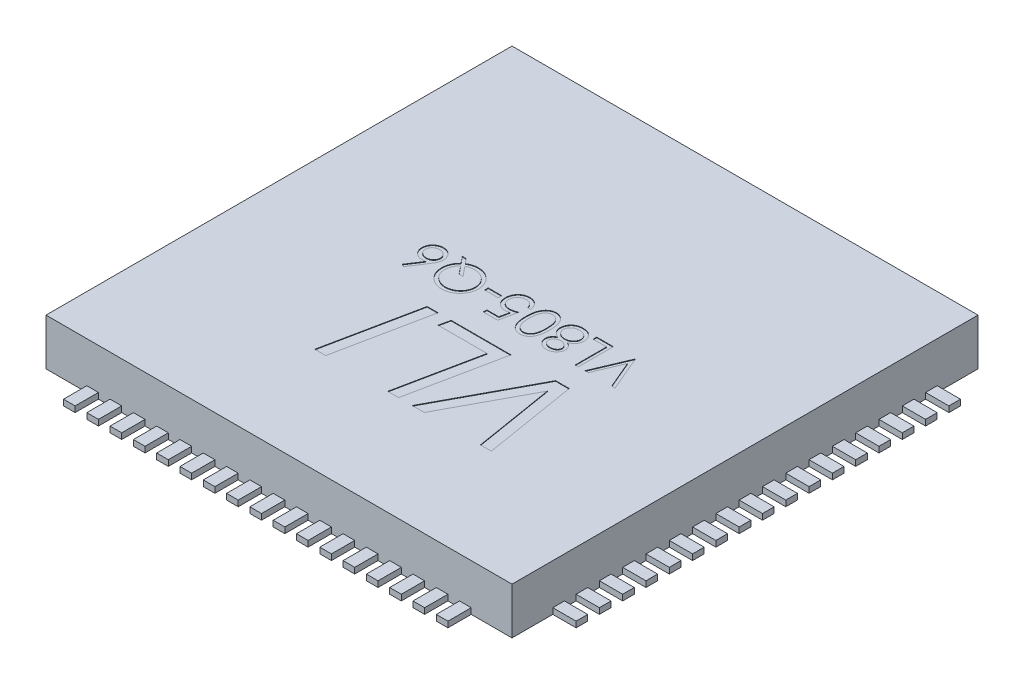
SolidWorks part; units mm, degrees
material "ABS"
ref_plane "Front Plane" through (0, 0, 0) normal (0, 0, 1) x (1, 0, 0)
ref_plane "Top Plane" through (0, 0, 0) normal (0, 1, 0) x (1, 0, 0)
ref_plane "Right Plane" through (0, 0, 0) normal (1, 0, 0) x (0, 0, -1)
sketch "BaseS" plane through (0, 0, 0) normal (0, 1, 0) x (1, 0, 0)
  line L1 (-4, 4) -> (4, 4)
  line L2 (-4, 4) -> (-4, -4)
  line L3 (-4, -4) -> (4, -4)
  line L4 (4, 4) -> (4, -4)
  line L5 (-4, 4) -> (4, -4) construction
  line L6 (-4, -4) -> (4, 4) construction
  point P0 (0, 0)
  dimension "W" = 8
  dimension "L" = 8
extrude "Base" add sketch "BaseS" along normal blind 0.8
sketch "TopNameS" plane through (0, 0.8, 0) normal (0, 1, 0) x (1, 0, 0)
  line L2 (-2, -0.6) -> (3, -0.6) construction
  line L5 (-4, -4) -> (4, -4) construction
  line L6 (4, -4) -> (4, 4) construction
  text T1 "<i>VLI</i>" font "Arial" height 1.6
  dimension "D1" = 5
  dimension "XDim" = 1
  dimension "YDim" = 3.4
sketch "PartNoAdditionalS" plane through (0, 0.8, 0) normal (0, 1, 0) x (1, 0, 0)
  line L0 (2, 0.4) -> (-3, 0.4) construction
  line L1 (4, 4) -> (-4, 4) construction
  line L2 (4, -4) -> (4, 4) construction
  text T0 "VL805-Q6" font "Century Gothic" height 0.6
  dimension "YDim" = 3.6
  dimension "TextWidth" = 5
  dimension "XDim" = 2
extrude "TopName" cut sketch "TopNameS" against normal blind 0.01
extrude "PartNoAdditional" cut sketch "PartNoAdditionalS" against normal blind 0.01
sketch "SolderConnectionS" plane through (0, 0, 0) normal (0, 1, 0) x (1, 0, 0)
  line L0 (4, -3.2) -> (4.4, -3.2)
  line L1 (4, -4) -> (4, 4) construction
  dimension "XDim" = 0.8
  dimension "Length" = 0.4
extrude "SolderConnection" add sketch "SolderConnectionS" along normal blind 0.1 thin thin type mid plane wall 0.2
pattern_linear "SC LP" count 17 spacing 0.4 along (0, 0, -1) of "SolderConnection"
ref_axis "AxisSC" through (0, 0.84, 0) along (0, -1, 0)
pattern_circular "SC CP" count 4 over 360 about axis through (0, 0.84, 0) along (0, -1, 0) of "SolderConnection", "SC LP"
